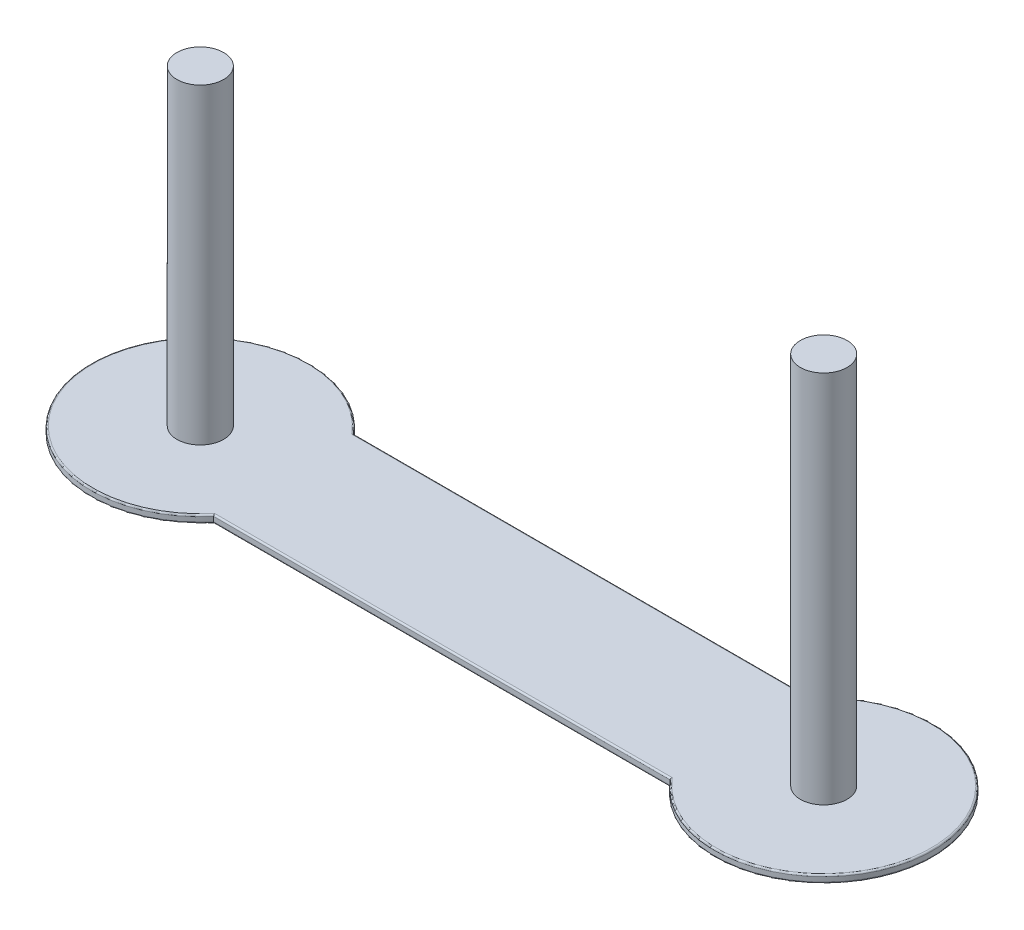
SolidWorks part; units mm, degrees
ref_plane "Front Plane" through (0, 0, 0) normal (0, 0, 1) x (1, 0, 0)
ref_plane "Top Plane" through (0, 0, 0) normal (0, 1, 0) x (1, 0, 0)
ref_plane "Right Plane" through (0, 0, 0) normal (1, 0, 0) x (0, 0, -1)
sketch "Sketch1" plane through (0, 0, 0) normal (0, 1, 0) x (1, 0, 0)
  line L0 (92.9519, 28.575) -> (-92.9519, 28.575)
  line L3 (-92.9519, -28.575) -> (92.9519, -28.575)
  arc A0 (92.9519, -28.575) -> (92.9519, 28.575) centre (127, 0) ccw
  arc A1 (-92.9519, -28.575) -> (-92.9519, 28.575) centre (-127, 0) cw
  point P0 (0, 0)
  dimension "D4" = 44.45
  dimension "D6" = 44.45
  dimension "D1" = 57.15
  dimension "D2" = 28.575
  dimension "D3" = 127
  dimension "D5" = 127
extrude "Boss-Extrude1" add sketch "Sketch1" along normal blind 3.175
sketch "Sketch2" plane through (0, 3.175, 0) normal (0, 1, 0) x (1, 0, 0)
  circle A0 centre (-127, 0) radius 9.525
  circle A1 centre (127, 0) radius 9.525
  dimension "D1" = 19.05
  dimension "D2" = 19.05
extrude "Boss-Extrude2" add sketch "Sketch2" along normal blind 127 contours A0
sketch "Sketch4" plane through (0, 3.175, 0) normal (0, 1, 0) x (1, 0, 0)
  circle A0 centre (127, 0) radius 9.525
  dimension "D1" = 19.05
extrude "Boss-Extrude3" add sketch "Sketch4" along normal blind 152.4
fillet "Fillet3" radius 0.635 8 edges at (0, 3.175, -28.575) (171.45, 3.175, 0) (0, 3.175, 28.575) (-171.45, 3.175, 0) (0, 0, -28.575) (171.45, 0, 0) (0, 0, 28.575) (-171.45, 0, 0)
